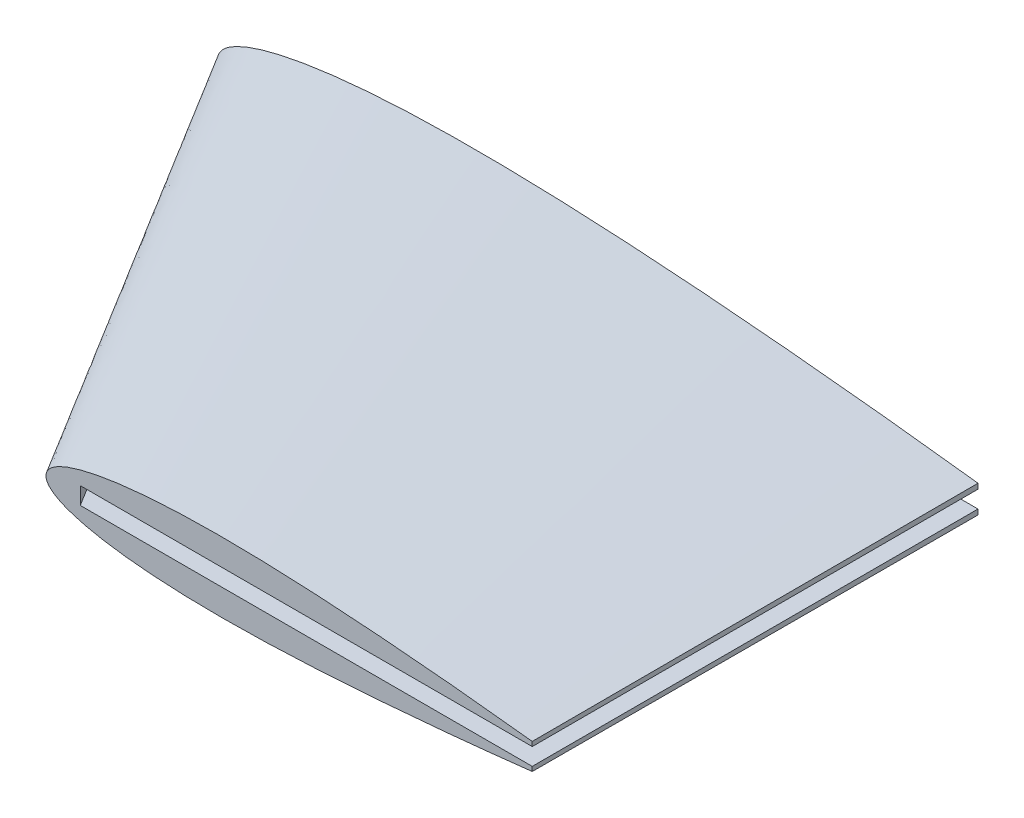
SolidWorks part; units mm, degrees
ref_plane "Front Plane" through (0, 0, 0) normal (0, 0, 1) x (1, 0, 0)
ref_plane "Top Plane" through (0, 0, 0) normal (0, 1, 0) x (1, 0, 0)
ref_plane "Right Plane" through (0, 0, 0) normal (1, 0, 0) x (0, 0, -1)
ref_plane "Plane1" through (0, 0, 82.55) normal (0, 0, 1) x (1, 0, 0)
curve "Curve1"
  spline degree 3 poles (25.4, 0.032, 0) (25.3951, 0.0327, 0) (25.3753, 0.0355, 0) (25.3309, 0.0417, 0) (25.257, 0.052, 0) (25.1537, 0.0664, 0) (25.0214, 0.0846, 0) (24.8603, 0.1068, 0) (24.6708, 0.1326, 0) (24.4533, 0.1619, 0) (24.2084, 0.1946, 0) (23.9366, 0.2304, 0) (23.6385, 0.2691, 0) (23.3149, 0.3106, 0) (22.9666, 0.3545, 0) (22.5942, 0.4008, 0) (22.1987, 0.449, 0) (21.7811, 0.499, 0) (21.3422, 0.5505, 0) (20.8832, 0.6032, 0) (20.405, 0.6571, 0) (19.9089, 0.7116, 0) (19.3959, 0.7667, 0) (18.8673, 0.8219, 0) (18.3242, 0.8772, 0) (17.7681, 0.9321, 0) (17.2001, 0.9864, 0) (16.6216, 1.0399, 0) (16.0339, 1.0922, 0) (15.4384, 1.143, 0) (14.8366, 1.1921, 0) (14.2297, 1.2391, 0) (13.6193, 1.2836, 0) (13.0067, 1.3254, 0) (12.3935, 1.3642, 0) (11.7809, 1.3995, 0) (11.1705, 1.4311, 0) (10.5636, 1.4587, 0) (9.9618, 1.4818, 0) (9.3663, 1.5004, 0) (8.7786, 1.514, 0) (8.2001, 1.5224, 0) (7.632, 1.5254, 0) (7.0758, 1.5227, 0) (6.5327, 1.5144, 0) (6.0041, 1.5, 0) (5.491, 1.4798, 0) (4.9948, 1.4535, 0) (4.5166, 1.4212, 0) (4.0575, 1.3829, 0) (3.6185, 1.3388, 0) (3.2008, 1.2888, 0) (2.8052, 1.2334, 0) (2.4327, 1.1725, 0) (2.0841, 1.1064, 0) (1.7603, 1.0355, 0) (1.462, 0.96, 0) (1.1898, 0.8801, 0) (0.9445, 0.7962, 0) (0.7264, 0.7086, 0) (0.536, 0.6175, 0) (0.3737, 0.523, 0) (0.2396, 0.4254, 0) (0.1341, 0.3245, 0) (0.0574, 0.22, 0) (0.0105, 0.1114, 0) (-0.0051, 0, 0) (0.0105, -0.1114, 0) (0.0574, -0.22, 0) (0.1341, -0.3245, 0) (0.2396, -0.4254, 0) (0.3737, -0.523, 0) (0.536, -0.6175, 0) (0.7264, -0.7086, 0) (0.9445, -0.7962, 0) (1.1898, -0.8801, 0) (1.462, -0.96, 0) (1.7603, -1.0355, 0) (2.0841, -1.1064, 0) (2.4327, -1.1725, 0) (2.8052, -1.2334, 0) (3.2008, -1.2888, 0) (3.6185, -1.3388, 0) (4.0575, -1.3829, 0) (4.5166, -1.4212, 0) (4.9948, -1.4535, 0) (5.491, -1.4798, 0) (6.0041, -1.5, 0) (6.5327, -1.5144, 0) (7.0758, -1.5227, 0) (7.632, -1.5254, 0) (8.2001, -1.5224, 0) (8.7786, -1.514, 0) (9.3663, -1.5004, 0) (9.9618, -1.4818, 0) (10.5636, -1.4587, 0) (11.1705, -1.4311, 0) (11.7809, -1.3995, 0) (12.3935, -1.3642, 0) (13.0067, -1.3254, 0) (13.6193, -1.2836, 0) (14.2297, -1.2391, 0) (14.8366, -1.1921, 0) (15.4384, -1.143, 0) (16.0339, -1.0922, 0) (16.6216, -1.0399, 0) (17.2001, -0.9864, 0) (17.7681, -0.9321, 0) (18.3242, -0.8772, 0) (18.8673, -0.8219, 0) (19.3959, -0.7667, 0) (19.9089, -0.7116, 0) (20.405, -0.6571, 0) (20.8832, -0.6032, 0) (21.3422, -0.5505, 0) (21.7811, -0.499, 0) (22.1987, -0.449, 0) (22.5942, -0.4008, 0) (22.9666, -0.3545, 0) (23.3149, -0.3106, 0) (23.6385, -0.2691, 0) (23.9366, -0.2304, 0) (24.2084, -0.1946, 0) (24.4533, -0.1619, 0) (24.6708, -0.1326, 0) (24.8603, -0.1068, 0) (25.0214, -0.0846, 0) (25.1537, -0.0664, 0) (25.257, -0.052, 0) (25.3309, -0.0417, 0) (25.3753, -0.0355, 0) (25.3951, -0.0327, 0) (25.4, -0.032, 0) knots 0 0 0 0 0.000289 0.001156 0.002598 0.004612 0.007194 0.010336 0.014031 0.018272 0.023046 0.028343 0.03415 0.040454 0.047238 0.054489 0.062187 0.070314 0.078852 0.08778 0.097078 0.106722 0.116691 0.126961 0.137507 0.148306 0.159331 0.170556 0.181957 0.193504 0.205171 0.216932 0.228758 0.240621 0.252495 0.26435 0.276161 0.287898 0.299536 0.311047 0.322405 0.333584 0.344559 0.355306 0.3658 0.376018 0.385937 0.395538 0.404798 0.413699 0.422221 0.430349 0.438066 0.445357 0.452209 0.458612 0.464554 0.47003 0.475035 0.479569 0.483637 0.48725 0.490431 0.493219 0.495674 0.497891 0.5 0.502109 0.504326 0.506781 0.509569 0.51275 0.516363 0.520431 0.524965 0.52997 0.535446 0.541388 0.547791 0.554643 0.561934 0.569651 0.577779 0.586301 0.595202 0.604462 0.614063 0.623982 0.6342 0.644694 0.655441 0.666416 0.677595 0.688953 0.700464 0.712102 0.723839 0.73565 0.747505 0.759379 0.771242 0.783068 0.794829 0.806496 0.818043 0.829444 0.840669 0.851694 0.862493 0.873039 0.883309 0.893278 0.902922 0.91222 0.921148 0.929686 0.937813 0.945511 0.952762 0.959546 0.96585 0.971657 0.976954 0.981728 0.985969 0.989664 0.992806 0.995388 0.997402 0.998844 0.999711 1 1 1 1
sketch "Sketch1" plane through (0, 0, 82.55) normal (0, 0, 1) x (1, 0, 0)
  line L0 (158.75, -0.136) -> (158.75, 0.136)
  line L1 (158.75, 0) -> (50.8, 0) construction
  spline S1 degree 3 poles (158.75, 0.136) (158.729, 0.139) (158.645, 0.1508) (158.3098, 0.1976) (157.8081, 0.2677) (157.1408, 0.3597) (156.4561, 0.4539) (155.6507, 0.5636) (154.7264, 0.6881) (153.6855, 0.8269) (152.5304, 0.9791) (151.2638, 1.1439) (149.8885, 1.3199) (147.8475, 1.5775) (145.6729, 1.8449) (143.3696, 2.1206) (141.5045, 2.3396) (139.5535, 2.5638) (137.5214, 2.7925) (135.4127, 3.0242) (133.2325, 3.2583) (130.9859, 3.493) (128.678, 3.728) (126.3143, 3.9613) (123.9003, 4.1924) (121.4416, 4.4195) (118.944, 4.642) (116.4133, 4.8579) (113.8554, 5.0664) (111.2763, 5.2661) (108.682, 5.4554) (106.0786, 5.6331) (103.4722, 5.7978) (100.009, 5.9975) (96.5614, 6.1659) (92.3047, 6.3299) (88.9536, 6.4222) (85.6503, 6.4702) (83.2361, 6.4828) (80.8722, 6.4716) (78.5642, 6.4361) (76.3173, 6.3752) (74.1369, 6.2891) (72.028, 6.1773) (69.9956, 6.0401) (68.0443, 5.8775) (66.1788, 5.6897) (64.4033, 5.4775) (62.7221, 5.2418) (61.1389, 4.983) (59.6575, 4.7024) (58.2813, 4.401) (57.0135, 4.0799) (55.8569, 3.7406) (54.814, 3.384) (53.887, 3.0115) (53.0779, 2.6242) (52.3881, 2.2228) (51.8184, 1.808) (51.37, 1.3792) (51.0439, 0.9351) (50.8445, 0.4736) (50.7783, 0) (50.8445, -0.4736) (51.0439, -0.9351) (51.37, -1.3792) (51.8184, -1.808) (52.3881, -2.2228) (53.0779, -2.6242) (53.887, -3.0115) (54.814, -3.384) (55.8569, -3.7406) (57.0135, -4.0799) (58.2813, -4.401) (59.6575, -4.7024) (61.1389, -4.983) (62.7221, -5.2418) (64.4033, -5.4775) (66.1788, -5.6897) (68.0443, -5.8775) (69.9956, -6.0401) (72.028, -6.1773) (74.1369, -6.2891) (76.3173, -6.3752) (78.5642, -6.4361) (80.8722, -6.4716) (83.2361, -6.4828) (85.6503, -6.4702) (88.9536, -6.4222) (93.1656, -6.3061) (97.4217, -6.1264) (100.8688, -5.9479) (103.4722, -5.7978) (106.0786, -5.6331) (108.682, -5.4554) (111.2763, -5.2661) (113.8554, -5.0664) (116.4133, -4.8579) (118.944, -4.642) (121.4416, -4.4195) (123.9003, -4.1924) (126.3143, -3.9613) (128.678, -3.728) (130.9859, -3.493) (133.2325, -3.2583) (135.4127, -3.0242) (137.5214, -2.7925) (139.5535, -2.5638) (141.5045, -2.3396) (143.3696, -2.1206) (145.6729, -1.8449) (147.8475, -1.5775) (149.8885, -1.3199) (151.2638, -1.1439) (152.5304, -0.9791) (153.6855, -0.8269) (154.7264, -0.6881) (155.6507, -0.5636) (156.4561, -0.4539) (157.1408, -0.3597) (157.8081, -0.2677) (158.3098, -0.1976) (158.645, -0.1508) (158.729, -0.139) (158.75, -0.136) knots 0 0 0 0 0.000289 0.001156 0.004612 0.007194 0.010336 0.014031 0.018272 0.023046 0.028343 0.03415 0.040454 0.047238 0.062187 0.070314 0.078852 0.08778 0.097078 0.106722 0.116691 0.126961 0.137507 0.148306 0.159331 0.170556 0.181957 0.193504 0.205171 0.216932 0.228758 0.240621 0.252495 0.26435 0.287898 0.299536 0.322405 0.333584 0.344559 0.355306 0.3658 0.376018 0.385937 0.395538 0.404798 0.413699 0.422221 0.430349 0.438066 0.445357 0.452209 0.458612 0.464554 0.47003 0.475035 0.479569 0.483637 0.48725 0.490431 0.493219 0.495674 0.497891 0.5 0.502109 0.504326 0.506781 0.509569 0.51275 0.516363 0.520431 0.524965 0.52997 0.535446 0.541388 0.547791 0.554643 0.561934 0.569651 0.577779 0.586301 0.595202 0.604462 0.614063 0.623982 0.6342 0.644694 0.655441 0.666416 0.677595 0.700464 0.723839 0.73565 0.747505 0.759379 0.771242 0.783068 0.794829 0.806496 0.818043 0.829444 0.840669 0.851694 0.862493 0.873039 0.883309 0.893278 0.902922 0.91222 0.921148 0.929686 0.937813 0.952762 0.959546 0.96585 0.971657 0.976954 0.981728 0.985969 0.989664 0.992806 0.995388 0.998844 0.999711 1 1 1 1
  point P2 (0, 0)
  dimension "D1" = 50.8
  dimension "D2" = 107.95
sketch "Sketch2" plane through (0, 0, 0) normal (0, 0, 1) x (1, 0, 0)
  line L0 (158.75, 0.2) -> (158.75, -0.2)
  line L1 (158.75, 0) -> (0, 0) construction
  spline S1 degree 3 poles (158.75, 0.2) (158.7191, 0.2044) (158.5956, 0.2217) (158.1027, 0.2906) (157.3648, 0.3937) (156.3836, 0.529) (155.3767, 0.6675) (154.1922, 0.8288) (152.833, 1.0119) (151.3023, 1.2161) (149.6035, 1.4399) (147.7408, 1.6822) (145.7184, 1.9411) (142.7169, 2.3199) (139.5189, 2.713) (136.1318, 3.1185) (133.389, 3.4406) (130.5199, 3.7702) (127.5314, 4.1066) (124.4304, 4.4474) (121.2243, 4.7916) (117.9204, 5.1368) (114.5265, 5.4823) (111.0504, 5.8255) (107.5004, 6.1653) (103.8848, 6.4993) (100.2118, 6.8264) (96.4902, 7.144) (92.7286, 7.4506) (88.9358, 7.7443) (85.1206, 8.0227) (81.2921, 8.284) (77.4592, 8.5262) (72.3662, 8.8198) (67.2961, 9.0676) (61.0363, 9.3086) (56.1082, 9.4444) (51.2504, 9.5149) (47.7001, 9.5335) (44.2239, 9.5171) (40.8297, 9.4649) (37.5255, 9.3753) (34.319, 9.2487) (31.2177, 9.0843) (28.2288, 8.8825) (25.3593, 8.6433) (22.6158, 8.3672) (20.0049, 8.0552) (17.5324, 7.7086) (15.2043, 7.328) (13.0258, 6.9153) (11.0019, 6.4721) (9.1375, 5.9999) (7.4366, 5.5008) (5.9029, 4.9765) (4.5397, 4.4287) (3.3498, 3.8591) (2.3354, 3.2688) (1.4977, 2.6588) (0.8382, 2.0282) (0.3587, 1.3751) (0.0655, 0.6964) (-0.0319, 0) (0.0655, -0.6964) (0.3587, -1.3751) (0.8382, -2.0282) (1.4977, -2.6588) (2.3354, -3.2688) (3.3498, -3.8591) (4.5397, -4.4287) (5.9029, -4.9765) (7.4366, -5.5008) (9.1375, -5.9999) (11.0019, -6.4721) (13.0258, -6.9153) (15.2043, -7.328) (17.5324, -7.7086) (20.0049, -8.0552) (22.6158, -8.3672) (25.3593, -8.6433) (28.2288, -8.8825) (31.2177, -9.0843) (34.319, -9.2487) (37.5255, -9.3753) (40.8297, -9.4649) (44.2239, -9.5171) (47.7001, -9.5335) (51.2504, -9.5149) (56.1082, -9.4444) (62.3024, -9.2737) (68.5614, -9.0094) (73.6306, -8.7469) (77.4592, -8.5262) (81.2921, -8.284) (85.1206, -8.0227) (88.9358, -7.7443) (92.7286, -7.4506) (96.4902, -7.144) (100.2118, -6.8264) (103.8848, -6.4993) (107.5004, -6.1653) (111.0504, -5.8255) (114.5265, -5.4823) (117.9204, -5.1368) (121.2243, -4.7916) (124.4304, -4.4474) (127.5314, -4.1066) (130.5199, -3.7702) (133.389, -3.4406) (136.1318, -3.1185) (139.5189, -2.713) (142.7169, -2.3199) (145.7184, -1.9411) (147.7408, -1.6822) (149.6035, -1.4399) (151.3023, -1.2161) (152.833, -1.0119) (154.1922, -0.8288) (155.3767, -0.6675) (156.3836, -0.529) (157.3648, -0.3937) (158.1027, -0.2906) (158.5956, -0.2217) (158.7191, -0.2044) (158.75, -0.2) knots 0 0 0 0 0.000289 0.001156 0.004612 0.007194 0.010336 0.014031 0.018272 0.023046 0.028343 0.03415 0.040454 0.047238 0.062187 0.070314 0.078852 0.08778 0.097078 0.106722 0.116691 0.126961 0.137507 0.148306 0.159331 0.170556 0.181957 0.193504 0.205171 0.216932 0.228758 0.240621 0.252495 0.26435 0.287898 0.299536 0.322405 0.333584 0.344559 0.355306 0.3658 0.376018 0.385937 0.395538 0.404798 0.413699 0.422221 0.430349 0.438066 0.445357 0.452209 0.458612 0.464554 0.47003 0.475035 0.479569 0.483637 0.48725 0.490431 0.493219 0.495674 0.497891 0.5 0.502109 0.504326 0.506781 0.509569 0.51275 0.516363 0.520431 0.524965 0.52997 0.535446 0.541388 0.547791 0.554643 0.561934 0.569651 0.577779 0.586301 0.595202 0.604462 0.614063 0.623982 0.6342 0.644694 0.655441 0.666416 0.677595 0.700464 0.723839 0.73565 0.747505 0.759379 0.771242 0.783068 0.794829 0.806496 0.818043 0.829444 0.840669 0.851694 0.862493 0.873039 0.883309 0.893278 0.902922 0.91222 0.921148 0.929686 0.937813 0.952762 0.959546 0.96585 0.971657 0.976954 0.981728 0.985969 0.989664 0.992806 0.995388 0.998844 0.999711 1 1 1 1
  dimension "D1" = 158.75
loft "Loft1" add profiles "Sketch2", "Sketch1" connector at (158.75, 0.2, 0) connector at (158.75, 0.136, 82.55)
sketch "Sketch3" plane through (0, 0, 0) normal (0, 1, 0) x (1, 0, 0)
  line L0 (158.75, 0) -> (6.35, 0)
  line L1 (158.75, 0) -> (0, 0) construction
  line L2 (6.35, 0) -> (57.15, -82.55)
  line L3 (50.8, -82.55) -> (158.75, -82.55) construction
  line L4 (57.15, -82.55) -> (158.75, -82.55)
  line L5 (158.75, -82.55) -> (158.75, 0)
  dimension "D1" = 152.4
  dimension "D2" = 101.6
extrude "Cut-Extrude1" cut sketch "Sketch3" against normal mid plane 3.175
sketch "Sketch4" plane through (0, 0, 0) normal (0, 1, 0) x (1, 0, 0)
  line L1 (140.8472, 0) -> (148.4672, 0)
  line L2 (140.8472, 0) -> (140.8472, -82.55)
  line L3 (140.8472, -82.55) -> (148.4672, -82.55)
  line L4 (148.4672, 0) -> (148.4672, -82.55)
  dimension "D1" = 7.62
extrude "Cut-Extrude2" cut sketch "Sketch4" against normal through all both and the other way through all
